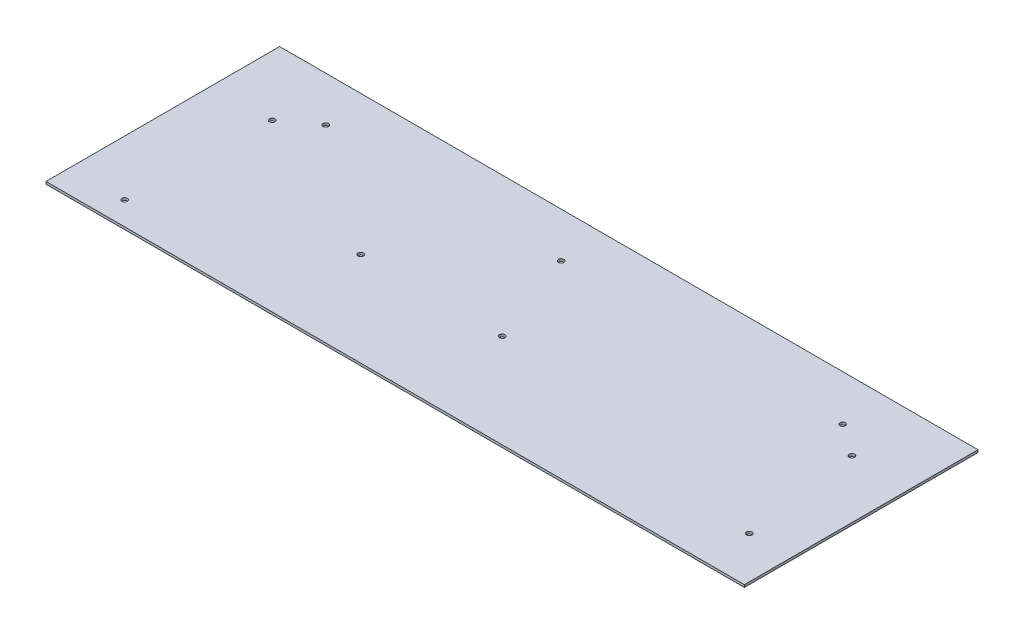
SolidWorks part; units mm, degrees
ref_plane "Front Plane" through (0, 0, 0) normal (0, 0, 1) x (1, 0, 0)
ref_plane "Top Plane" through (0, 0, 0) normal (0, 1, 0) x (1, 0, 0)
ref_plane "Right Plane" through (0, 0, 0) normal (1, 0, 0) x (0, 0, -1)
sketch "PCB Reference" plane through (0, 0, 0) normal (0, 1, 0) x (1, 0, 0)
  line L0 (23.8283, 321.47) -> (23.8283, 416.47) construction
sketch "Sketch3" plane through (0, 0, 0) normal (0, 1, 0) x (1, 0, 0)
  line L0 (25.1001, 321.0145) -> (21.8389, 321.0145) construction
  line L1 (23.7657, 322.0207) -> (23.7657, 320.2296) construction
  line L3 (23.7657, 321.0145) -> (307.7657, 321.0145)
  line L4 (23.7657, 321.0145) -> (23.7657, 416.0145)
  line L5 (23.7657, 416.0145) -> (307.7657, 416.0145)
  line L6 (307.7657, 321.0145) -> (307.7657, 416.0145)
  point P0 (0, 320.6934)
  point P1 (23.7657, 322.0207)
  point P2 (25.1001, 321.0145)
  point P11 (46.2657, 330.5145)
  point P12 (48.2657, 388.5145)
  point P13 (60.7657, 397.7645)
  point P14 (113.5157, 359.2645)
  point P15 (171.0157, 359.2645)
  point P16 (156.5157, 397.7645)
  point P17 (271.2657, 397.5145)
  point P18 (284.2657, 388.2645)
  point P19 (290.7657, 340.0145)
  dimension "D1" = 95
  dimension "D2" = 284
  dimension "D3" = 22.5
  dimension "D4" = 9.5
  dimension "D5" = 24.5
  dimension "D6" = 67.5
  dimension "D7" = 76.75
  dimension "D8" = 37
  dimension "D9" = 89.75
  dimension "D10" = 38.25
  dimension "D11" = 38.25
  dimension "D12" = 147.25
  dimension "D13" = 17
  dimension "D14" = 19
  dimension "D15" = 23.5
  dimension "D16" = 27.75
  dimension "D17" = 36.5
  dimension "D18" = 18.5
  dimension "D19" = 18.25
  dimension "D20" = 132.75
extrude "Boss-Extrude1" add sketch "Sketch3" along normal blind 1
hole_wizard "Ø2.0mm Dowel Hole1" positions "Sketch4" profile "Sketch5" hole size "Ø2.0" standard "ANSI Metric" end condition through all
sketch "Sketch4" plane through (0, 1, 0) normal (0, 1, 0) x (1, 0, 0)
  point P0 (48.2657, 388.5145)
  point P3 (60.7657, 397.7645)
  point P6 (46.2657, 330.5145)
  point P9 (113.5157, 359.2645)
  point P12 (156.5157, 397.7645)
  point P15 (171.0157, 359.2645)
  point P18 (271.2657, 397.5145)
  point P21 (284.2657, 388.2645)
  point P24 (290.7657, 340.0145)
sketch "Sketch5" plane through (48.2657, 1, -388.5145) normal (1, 0, 0) x (0, 0, 1)
  line L0 (0, 0) -> (0, 1)
  line L1 (0, 1) -> (1.1, 1)
  line L2 (1.1, 1) -> (1.1, 0)
  line L5 (1.1, 0) -> (0, 0)
  line L11 (0, -6.35) -> (0, 107.95) construction
  dimension "Thru Hole Dia." = 2.2
  dimension "Thru Hole Depth" = 1
